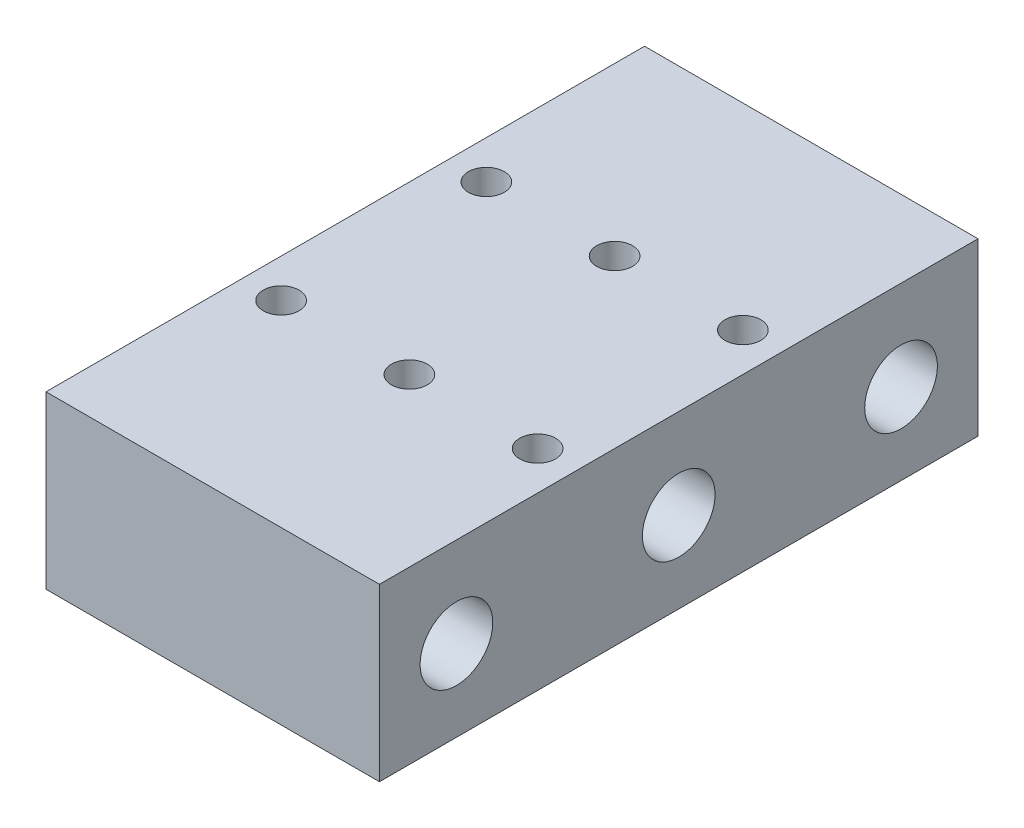
SolidWorks part; units mm, degrees
ref_plane "Plano frontal" through (0, 0, 0) normal (0, 0, 1) x (1, 0, 0)
ref_plane "Plano superior" through (0, 0, 0) normal (0, 1, 0) x (1, 0, 0)
ref_plane "Plano direito" through (0, 0, 0) normal (1, 0, 0) x (0, 0, -1)
sketch "Esboço1" plane through (0, 0, 0) normal (0, 1, 0) x (1, 0, 0)
  line L1 (-19.5, -35) -> (19.5, -35)
  line L2 (-19.5, -35) -> (-19.5, 35)
  line L3 (-19.5, 35) -> (19.5, 35)
  line L4 (19.5, -35) -> (19.5, 35)
  line L5 (-19.5, -35) -> (19.5, 35) construction
  line L6 (-19.5, 35) -> (19.5, -35) construction
  point P0 (0, 0)
  dimension "D1" = 39
  dimension "D2" = 70
base flange "Flange-base1" sketch "Esboço1" thickness 20 reverse thickness direction no parameters "D1"=10
sketch "Esboço6" plane through (0, 0, 0) normal (0, 1, 0) x (1, 0, 0)
  line L0 (0, -12) -> (0, 12) construction
  line L1 (0, 12) -> (15, 12) construction
  line L2 (0, 12) -> (-15, 12) construction
  line L3 (0, -12) -> (15, -12) construction
  line L4 (0, -12) -> (-15, -12) construction
  circle A0 centre (-15, 12) radius 2.1
  circle A1 centre (15, 12) radius 2.1
  circle A2 centre (0, 12) radius 2.1
  circle A3 centre (-15, -12) radius 2.1
  circle A4 centre (0, -12) radius 2.1
  circle A5 centre (15, -12) radius 2.1
  point P4 (0, 0)
extrude "Corte-extrusão1" cut sketch "Esboço6" against normal blind 15
sketch "Esboço8" plane through (-19.5, 0, 0) normal (-1, 0, 0) x (0, 0, 1)
  circle A0 centre (-26, -10.5) radius 4.25
  circle A1 centre (26, -10.5) radius 4.25
  circle A2 centre (0, -10.5) radius 4.25
extrude "Corte-extrusão2" cut sketch "Esboço8" against normal blind 39 normal cut yes
sketch "Curva-Linhas1" [suppressed] plane through (0, 0, 0) normal (0, 1, 0) x (1, 0, 0)
sketch "Caixa delimitadora1" [suppressed] plane through (0, 0, 0) normal (0, 1, 0) x (1, 0, 0)
sheet metal parameters "Chapa metálica1" thickness 20 parameters "D1"=10
flat pattern "Padrão-Plano1" [suppressed]
sketch "Curva-Linhas2" plane through (0, 0, 0) normal (0, 1, 0) x (1, 0, 0)
sketch "Caixa delimitadora2" [suppressed] plane through (0, 0, 0) normal (0, 1, 0) x (1, 0, 0)
sheet metal parameters "Chapa metálica2" thickness 20 parameters "D1"=10
flat pattern "Padrão-Plano1"
sketch "Curva-Linhas2" plane through (0, 0, 0) normal (0, 1, 0) x (1, 0, 0)
sketch3d "Caixa delimitadora2" [suppressed]
  line L0 (-19.5, -35, 0) -> (-19.5, 35, 0) construction
  line L1 (19.5, -35, 0) -> (19.5, 35, 0) construction
  line L2 (-19.5, -35, 0) -> (19.5, -35, 0) construction
  line L3 (-19.5, 35, 0) -> (19.5, 35, 0) construction
sheet metal parameters "Chapa metálica4" thickness 20 parameters "D1"=10
flat pattern "Padrão-Plano1"
sketch "Curva-Linhas2" plane through (0, 0, 0) normal (0, 1, 0) x (1, 0, 0)
sketch3d "Caixa delimitadora2" [suppressed]
  line L0 (-19.5, -35, 0) -> (-19.5, 35, 0) construction
  line L1 (19.5, -35, 0) -> (19.5, 35, 0) construction
  line L2 (-19.5, -35, 0) -> (19.5, -35, 0) construction
  line L3 (-19.5, 35, 0) -> (19.5, 35, 0) construction
